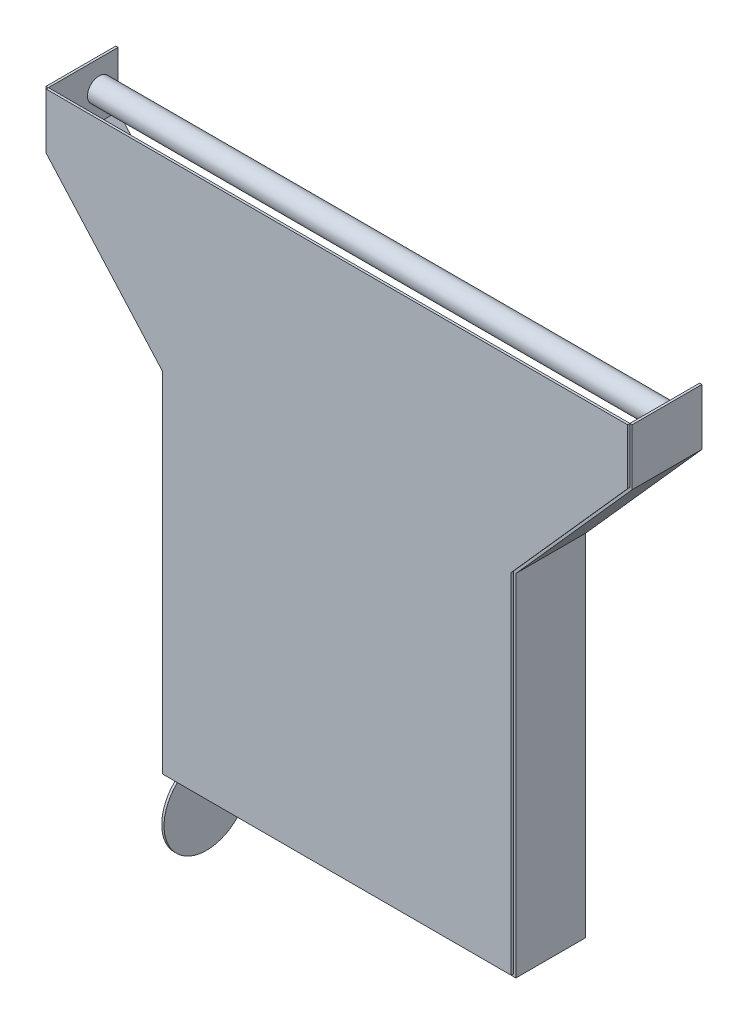
SolidWorks part; units mm, degrees
ref_plane "Front Plane" through (0, 0, 0) normal (0, 0, 1) x (1, 0, 0)
ref_plane "Top Plane" through (0, 0, 0) normal (0, 1, 0) x (1, 0, 0)
ref_plane "Right Plane" through (0, 0, 0) normal (1, 0, 0) x (0, 0, -1)
sketch "Sketch1" plane through (0, 0, 0) normal (0, 0, 1) x (1, 0, 0)
  line L0 (317.5, 41.0958) -> (190.5, -101.6)
  line L1 (-317.5, 101.6) -> (317.5, 101.6)
  line L2 (-317.5, 101.6) -> (-317.5, -101.6)
  line L3 (-317.5, -101.6) -> (317.5, -101.6)
  line L4 (317.5, 101.6) -> (317.5, -101.6)
  line L5 (-317.5, 101.6) -> (317.5, -101.6) construction
  line L6 (-317.5, -101.6) -> (317.5, 101.6) construction
  line L7 (0, 101.6) -> (0, -101.6) construction
  line L8 (-317.5, 41.0958) -> (-190.5, -101.6)
  line L10 (190.5, -101.6) -> (-190.5, -101.6)
  line L11 (190.5, -101.6) -> (190.5, -482.6)
  line L12 (190.5, -482.6) -> (-190.5, -482.6)
  line L13 (-190.5, -101.6) -> (-190.5, -482.6)
  point P0 (0, 0)
  dimension "D1" = 635
  dimension "D2" = 203.2
  dimension "D3" = 381
  dimension "D4" = 381
extrude "Boss-Extrude1" add sketch "Sketch1" along normal blind 2.54 contours L2 L8 L3 L0 L4 L1 | L3 L13 L12 L11 region at (0, 8.8291, 0) region at (0, -292.1, 0)
sketch "Sketch2" plane through (317.5, 0, 0) normal (1, 0, 0) x (0, 0, -1)
  line L0 (-2.54, 41.0958) -> (0, 41.0958) construction
  line L1 (-2.54, 101.6) -> (99.06, 101.6)
  line L2 (-2.54, 101.6) -> (-2.54, 41.0958)
  line L3 (-2.54, 41.0958) -> (99.06, 41.0958)
  line L4 (99.06, 101.6) -> (99.06, 41.0958)
  dimension "D1" = 101.6
extrude "Boss-Extrude2" [suppressed] add sketch "Sketch2" against normal blind 2.54 separate body
mirror "Mirror1" [suppressed] about plane through (0, 0, 0) normal (1, 0, 0)
mirror "Mirror2" [suppressed] about plane through (0, 0, 0) normal (1, 0, 0) of bodies 102
sketch "Sketch3" [suppressed] plane through (304.8, 0, 0) normal (1, 0, 0) x (0, 0, -1)
  line L0 (48.26, 73.9855) -> (-2.54, 73.9855) construction
  line L4 (-2.54, 101.6) -> (-2.54, 41.0958)
  line L5 (-2.54, 41.0958) -> (99.06, 41.0958)
  line L6 (99.06, 41.0958) -> (99.06, 101.6)
  line L7 (99.06, 101.6) -> (-2.54, 101.6)
  line L8 (-2.54, 101.6) -> (-2.54, 41.0958)
  line L9 (-2.54, 41.0958) -> (99.06, 41.0958)
  line L10 (99.06, 41.0958) -> (99.06, 101.6)
  line L11 (99.06, 101.6) -> (-2.54, 101.6)
  circle A0 centre (60.96, 73.9855) radius 12.7
  dimension "D2" = 25.4
  dimension "D3" = 50.8
  dimension "D1" = 0
extrude "Boss-Extrude3" [suppressed] add sketch "Sketch3" against normal up to surface (604.52 mm away) from surface separate body contours A0
sketch "Sketch4" plane through (0, 0, 0) normal (0, 0, -1) x (-1, 0, 0)
  line L8 (317.5, 41.0958) -> (317.5, 101.6)
  line L9 (317.5, 101.6) -> (-317.5, 101.6)
  line L10 (-317.5, 101.6) -> (-317.5, 41.0958)
  line L11 (-317.5, 41.0958) -> (-190.5, -101.6)
  line L12 (-317.5, 41.0958) -> (-190.5, -101.6)
  line L13 (-190.5, -482.6) -> (190.5, -482.6)
  line L14 (-190.5, -101.6) -> (-190.5, -482.6)
  line L15 (-190.5, -101.6) -> (-190.5, -482.6)
  line L16 (317.5, 41.0958) -> (317.5, 101.6)
  line L18 (-317.5, 101.6) -> (-317.5, 41.0958)
  line L21 (-190.5, -482.6) -> (190.5, -482.6)
  line L24 (190.5, -482.6) -> (190.5, -101.6)
  line L25 (190.5, -482.6) -> (190.5, -101.6)
  line L26 (190.5, -101.6) -> (317.5, 41.0958)
  line L27 (190.5, -101.6) -> (317.5, 41.0958)
  dimension "D1" = 0
extrude "Extrude-Thin1" add sketch "Sketch4" along normal blind 76.2 separate body thin thin type one direction wall 2.54
sketch "Sketch5" plane through (-317.5, 0, 0) normal (1, 0, 0) x (0, 0, -1)
  line L0 (42.6648, 72.2881) -> (0, 71.3479) construction
  line L1 (0, 41.0958) -> (0, 101.6) construction
  circle A0 centre (55.3648, 72.2881) radius 12.7
  dimension "D1" = 25.4
extrude "Boss-Extrude4" add sketch "Sketch5" along normal up to next
sketch "Sketch6" plane through (-190.5, 0, 0) normal (1, 0, 0) x (0, 0, -1)
  line L0 (47.625, -133.404) -> (0, -133.404) construction
  line L1 (0, -101.6) -> (0, -482.6) construction
  circle A0 centre (60.325, -133.404) radius 12.7
  circle A1 centre (55.3648, 72.2881) radius 12.7 construction
  dimension "D1" = 47.625
extrude "Boss-Extrude5" [suppressed] add sketch "Sketch6" along normal up to next separate body
move or copy body "Body-Move/Copy1" [suppressed] bodies to move or copy 108 copy yes number of copies 1 translate (0, -304.8, 0)
sketch "Sketch8" [suppressed] plane through (0, 0, 0) normal (1, 0, 0) x (0, 0, -1)
  line L0 (73.025, -133.404) -> (73.025, -438.204)
  line L1 (47.625, -133.404) -> (47.625, -438.204)
  circle A0 centre (60.325, -133.404) radius 12.7
  arc A1 (73.025, -133.404) -> (47.625, -133.404) centre (60.325, -133.404) ccw
  circle A2 centre (60.325, -438.204) radius 12.7
  arc A3 (47.625, -438.204) -> (73.025, -438.204) centre (60.325, -438.204) ccw
extrude "Extrude-Thin2" [suppressed] add sketch "Sketch8" along normal blind 24.638 thin thin type mid plane wall 2.54
sketch "Sketch9" plane through (-190.5, -297.8601, 89.6251) normal (1, 0, 0) x (0, 0, -1)
  circle A0 centre (132.8231, -232.3061) radius 46.4086
extrude "Boss-Extrude6" add sketch "Sketch9" along normal blind 2.54 separate body
